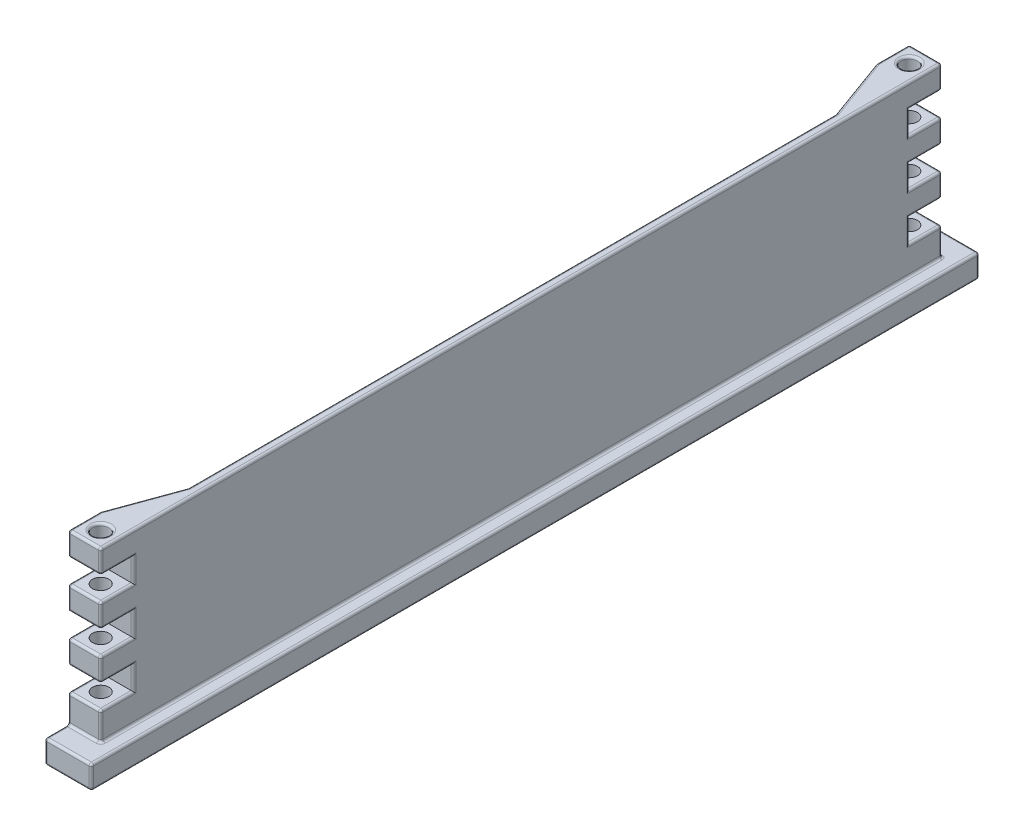
SolidWorks part; units mm, degrees
ref_plane "Front Plane" through (0, 0, 0) normal (0, 0, 1) x (1, 0, 0)
ref_plane "Top Plane" through (0, 0, 0) normal (0, 1, 0) x (1, 0, 0)
ref_plane "Right Plane" through (0, 0, 0) normal (1, 0, 0) x (0, 0, -1)
sketch "Sketch1" plane through (0, 0, 0) normal (1, 0, 0) x (0, 0, -1)
  line L1 (-45, -20.5) -> (45, -20.5)
  line L2 (-45, -4.5) -> (-45, 0.5)
  line L3 (-38, 20.5) -> (45, 20.5)
  line L4 (45, -20.5) -> (45, 20.5)
  line L5 (-45, -20.5) -> (45, 20.5) construction
  line L6 (-45, 20.5) -> (45, -20.5) construction
  line L7 (-50, -15.5) -> (-50, -20.5)
  line L8 (-50, -20.5) -> (-45, -20.5)
  line L12 (-38, 20.5) -> (-38, 15.5) construction
  line L13 (-38, 15.5) -> (-45, 15.5)
  line L14 (-38, 15.5) -> (-38, 10.5)
  line L15 (-38, 10.5) -> (-45, 10.5)
  line L16 (-38, 10.5) -> (-38, 5.5) construction
  line L17 (-38, 5.5) -> (-38, 0.5)
  line L18 (-38, 0.5) -> (-38, -4.5) construction
  line L19 (-38, -4.5) -> (-38, -9.5)
  line L20 (-38, 20.5) -> (-45, 20.5)
  line L21 (-45, 15.5) -> (-45, 20.5)
  line L22 (-38, -9.5) -> (-45, -9.5)
  line L23 (-38, -4.5) -> (-45, -4.5)
  line L24 (-38, 0.5) -> (-45, 0.5)
  line L25 (-38, 5.5) -> (-45, 5.5)
  line L26 (-45, 5.5) -> (-45, 10.5)
  line L42 (-50, -15.5) -> (-45, -15.5)
  line L43 (-45, -15.5) -> (-45, -9.5)
  point P0 (0, 0)
  dimension "D1" = 41
  dimension "D2" = 90
  dimension "D3" = 5
  dimension "D4" = 7
  dimension "D5" = 5
  dimension "D6" = 5
extrude "Boss-Extrude1" add sketch "Sketch1" along normal blind 7 contours L19 L22 L2 L7 L8 L1 L4 L3 L12 L14 L16 L17 L18 | L18 L24 L2 L23 | L25 L16 L15 L2 | L13 L12 L3 L2 region at (0, -0.2119, -0.8781)
sketch "Sketch3" plane through (7, 0, 0) normal (1, 0, 0) x (0, 0, -1)
  line L3 (45, -20.5) -> (-50, -20.5)
  line L5 (-50, -15.5) -> (-50, -20.5)
  line L6 (-50, -15.5) -> (45, -15.5)
  line L7 (45, -20.5) -> (45, 20.5) construction
  line L8 (45, -15.5) -> (45, -20.5)
sketch "Sketch7" plane through (0, -20.5, 0) normal (0, -1, 0) x (1, 0, 0)
  line L0 (0, 45) -> (7, 45)
  line L1 (0, 50) -> (0, -45) construction
  line L3 (7, 45) -> (7, 38)
  line L4 (7, 38) -> (0, 38)
  line L5 (0, 38) -> (0, 45)
  line L6 (7, 50) -> (0, 50) construction
  line L8 (7, 38) -> (0, 45) construction
  line L10 (0.6788, 39.8625) -> (3.5075, 38.238)
  line L11 (3.5075, 38.238) -> (6.3287, 39.8755)
  line L12 (6.3287, 39.8755) -> (6.3212, 43.1375)
  line L13 (6.3212, 43.1375) -> (3.4925, 44.762)
  line L14 (3.4925, 44.762) -> (0.6713, 43.1245)
  line L15 (0.6713, 43.1245) -> (0.6788, 39.8625)
  circle A0 centre (3.5, 41.5) radius 1.75
  circle A1 centre (3.5, 41.5) radius 2.825 construction
  dimension "D4" = 5.65
  dimension "D5" = 3.5
  dimension "D1" = 5
  dimension "D2" = 7
  dimension "D3" = 7
extrude "Cut-Extrude3" cut sketch "Sketch7" against normal through all both and the other way through all contours A0 region at (3.5, -20.5, 41.5)
extrude "Boss-Extrude2" add sketch "Sketch3" along normal blind 3
extrude "Cut-Extrude4" cut sketch "Sketch7<3>" against normal blind 8 and the other way through all contours L14 L15 L10 L11 L12 L13 A0 region at (0.7614, -20.5, 41.4937)
sketch "Sketch7<3>" plane through (0, -20.5, 0) normal (0, -1, 0) x (1, 0, 0) same geometry as "Sketch7"
sketch "Sketch8" plane through (0, 20.5, 0) normal (0, 1, 0) x (1, 0, 0)
  line L0 (0, -38) -> (5, -24.2626)
  line L1 (0, -45) -> (0, 45) construction
  line L2 (5, -24.2626) -> (5, 45)
  line L3 (7, 45) -> (0, 45) construction
  line L4 (0, -38) -> (0, 45)
  line L5 (0, 45) -> (5, 45)
  dimension "D1" = 2
  dimension "D2" = 7
  dimension "D3" = 200
extrude "Cut-Extrude5" cut sketch "Sketch8" against normal blind 39
mirror "Mirror2" about plane through (7, 0, -45) normal (0, 0, 1) of bodies 111 109
fillet "Fillet1" radius 0.5 87 edges at (3.5, -9.5, 45) (3.5, -15.5, 45) (0, -12.5, 45) (5, -15.5, 50) (5, -20.5, 50) (0, -18, 50) (5, -20.5, -140) (5, -15.5, -140) (0, -18, -140) (3.5, -15.5, -135) (3.5, -9.5, -135) (0, -12.5, -135) (3.5, -4.5, -135) (3.5, 0.5, -135) (0, -2, -135) (3.5, 5.5, -135) (3.5, 10.5, -135) (0, 8, -135) (3.5, 15.5, -135) (0, 18, -135) (3.5, 15.5, 45) (0, 18, 45) (3.5, 10.5, 45) (3.5, 5.5, 45) (0, 8, 45) (3.5, 0.5, 45) (3.5, -4.5, 45) (0, -2, 45) (5, 1, 24.2626) (5, 1, -114.2626) (7, -9.5, 41.5) (7, -7, 38) (7, -4.5, 41.5) (7, -2, 45) (7, 0.5, 41.5) (7, 3, 38) (7, 5.5, 41.5) (7, 8, 45) (7, 10.5, 41.5) (7, 13, 38) (7, 15.5, 41.5) (7, 18, 45) (7, 18, -135) (7, 15.5, -131.5) (7, 13, -128) (7, 10.5, -131.5) (7, 8, -135) (7, 5.5, -131.5) (7, 3, -128) (7, 0.5, -131.5) (7, -2, -135) (7, -4.5, -131.5) (7, -7, -128) (7, -9.5, -131.5) (7, -12.5, -135) (7, -15.5, -45) (7, -12.5, 45) (3.5, 20.5, -129.75) (3.5, 20.5, 39.75) (5, 20.5, -45) (2.5, 20.5, -121.1313) (0, 20.5, -131.5) (3.5, 20.5, -135) (7, 20.5, -45) (3.5, 20.5, 45) (0, 20.5, 41.5) (2.5, 20.5, 31.1313) (0, -4.5, 41.5) (0, 0.5, 41.5) (0, 10.5, 41.5) (0, 15.5, 41.5) (0, -9.5, 41.5) (0, -15.5, 47.5) (0, 15.5, -131.5) (0, 10.5, -131.5) (0, 5.5, -131.5) (0, -4.5, -131.5) (0, 0.5, -131.5) (0, -9.5, -131.5) (0, -15.5, -137.5) (0, -20.5, -45) (5, -18.5, -45) (0, -18.5, -45) (10, -18, 50) (10, -18, -140) (10, -20.5, -45) (10, -15.5, -45)
